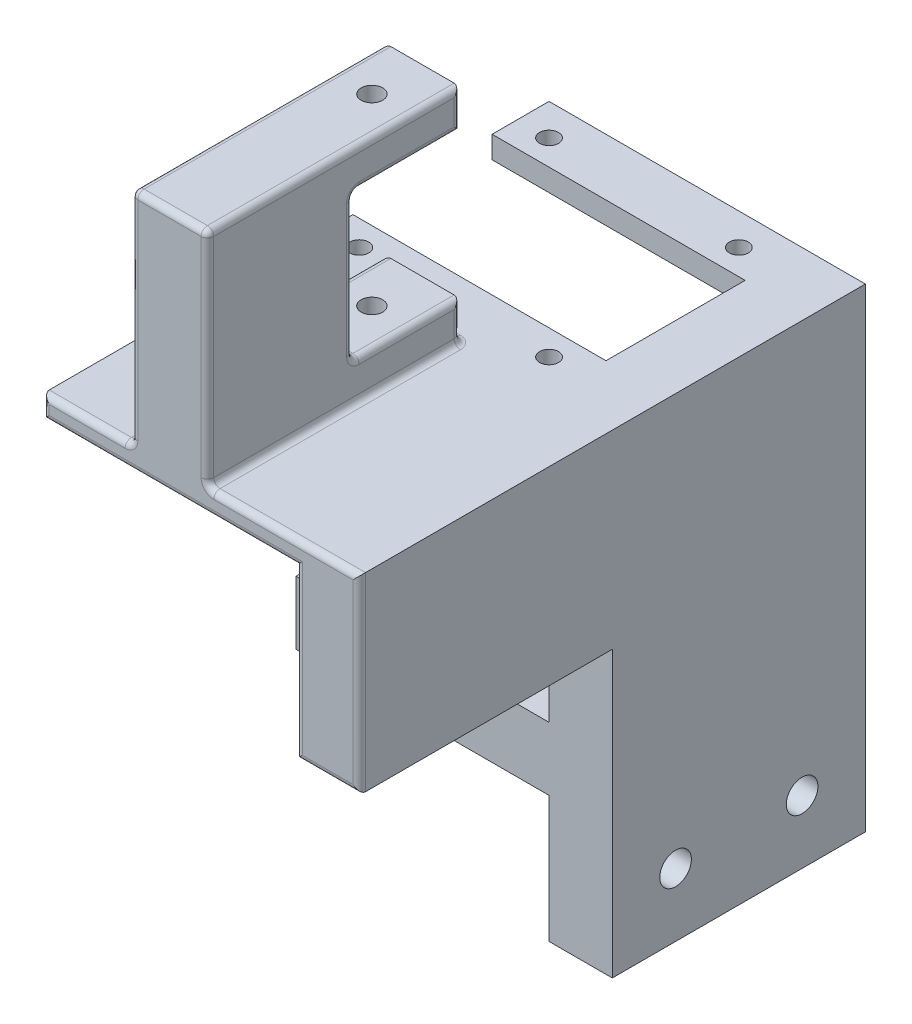
SolidWorks part; units mm, degrees
ref_plane "Front Plane" through (0, 0, 0) normal (0, 0, 1) x (1, 0, 0)
ref_plane "Top Plane" through (0, 0, 0) normal (0, 1, 0) x (1, 0, 0)
ref_plane "Right Plane" through (0, 0, 0) normal (1, 0, 0) x (0, 0, -1)
sketch "Sketch1" plane through (0, 0, 0) normal (1, 0, 0) x (0, 0, -1)
  line L0 (0, 27.5) -> (0, -27.5) construction
  line L5 (-20, 55) -> (20, 55)
  line L6 (-20, 55) -> (-20, 0)
  line L7 (-20, 0) -> (20, 0)
  line L8 (20, 55) -> (20, 0)
  line L9 (-20, 55) -> (20, 0) construction
  line L10 (-20, 0) -> (20, 55) construction
  line L11 (22, 0) -> (-22, 0) construction
  line L13 (-20, -20) -> (20, -20)
  line L14 (-20, -20) -> (-20, 0)
  line L15 (-20, 0) -> (20, 0)
  line L16 (20, -20) -> (20, 0)
  line L17 (-20, -20) -> (20, 0) construction
  line L18 (-20, 0) -> (20, -20) construction
  line L19 (10, -15) -> (-10, -15) construction
  line L20 (10, -15) -> (10, -5) construction
  line L21 (10, -5) -> (-10, -5) construction
  line L22 (-10, -15) -> (-10, -5) construction
  line L23 (10, -15) -> (-10, -5) construction
  line L24 (10, -5) -> (-10, -15) construction
  circle A0 centre (-10, -10) radius 2.5
  circle A1 centre (10, -10) radius 2.5
  point P1 (0, 27.5)
  point P10 (0, -10)
  point P11 (0, -10)
  dimension "D5" = 5
  dimension "D1" = 55
  dimension "D2" = 40
  dimension "D3" = 20
  dimension "D4" = 20
extrude "Boss-Extrude1" add sketch "Sketch1" along normal blind 10 contours L8 L5 L6 L7 | L13 L16 L7 L14 A1 A0 region at (0, 27.5, 0) region at (0, -10, 0)
sketch "Sketch3" plane through (0, 0, 0) normal (-1, 0, 0) x (0, 0, 1)
  line L0 (20, 55) -> (20, -20) construction
  line L1 (-20, 10) -> (20, 10)
  line L2 (-20, 10) -> (-20, 0)
  line L3 (-20, 0) -> (20, 0)
  line L4 (20, 10) -> (20, 0)
  line L5 (-20, 10) -> (20, 0) construction
  line L6 (-20, 0) -> (20, 10) construction
  dimension "D1" = 10
extrude "Boss-Extrude2" add sketch "Sketch3" along normal blind 40
sketch "Sketch4" plane through (0, 0, 0) normal (-1, 0, 0) x (0, 0, 1)
  line L13 (-20, 55) -> (-11, 55)
  line L14 (-20, 55) -> (-20, 51.5)
  line L15 (-20, 51.5) -> (-11, 51.5)
  line L16 (-11, 55) -> (-11, 51.5)
  dimension "D1" = 9
  dimension "D2" = 3.5
extrude "Boss-Extrude3" add sketch "Sketch4" along normal blind 40
sketch "Sketch5" plane through (0, 55, 0) normal (0, 1, 0) x (1, 0, 0)
  line L1 (-40, 20) -> (-35, 20) construction
  line L2 (-40, 20) -> (-40, 15) construction
  line L3 (-40, 15) -> (-35, 15) construction
  line L4 (-35, 20) -> (-35, 15) construction
  line L5 (10, 20) -> (-40, 20) construction
  line L7 (0, 20) -> (-5, 20) construction
  line L8 (0, 20) -> (0, 15) construction
  line L9 (0, 15) -> (-5, 15) construction
  line L10 (-5, 20) -> (-5, 15) construction
  circle A0 centre (-35, 15) radius 1.5
  circle A1 centre (-5, 15) radius 1.5
  dimension "D3" = 3
  dimension "D7" = 3
  dimension "D1" = 5
  dimension "D2" = 5
  dimension "D4" = 5
  dimension "D5" = 5
  dimension "D6" = 30
extrude "Cut-Extrude1" cut sketch "Sketch5" against normal up to next
mirror "Mirror2" about plane through (0, 0, 0) normal (0, 0, 1) of "Cut-Extrude1", "Boss-Extrude3"
sketch "Sketch7" plane through (0, 0, 20) normal (0, 0, 1) x (1, 0, 0)
  line L0 (0, -22) -> (0, 22) construction
  line L1 (-40, 55) -> (0, 55)
  line L2 (-40, 55) -> (-40, 51.5)
  line L3 (-40, 51.5) -> (0, 51.5)
  line L4 (0, 55) -> (0, 51.5)
  line L5 (-20, 51.5) -> (-20, 55) construction
  line L6 (-40, 53.25) -> (0, 53.25) construction
  line L7 (-40, 51.5) -> (0, 51.5) construction
  line L8 (10, 55) -> (10, -20) construction
  line L9 (0, 55) -> (10, 55)
  line L10 (0, 55) -> (0, 25)
  line L11 (0, 25) -> (10, 25)
  line L12 (10, 55) -> (10, 25)
  line L13 (5, 25) -> (5, 55) construction
  line L14 (0, 40) -> (10, 40) construction
  point P199 (5, 40)
  point P296 (-20, 53.25)
  line M2 (10, 55) -> (-40, 55)
  line M3 (-40, 55) -> (-40, 51.5)
  line M4 (-40, 51.5) -> (0, 51.5)
  line M5 (0, 51.5) -> (0, 10)
  line M11 (10, -20) -> (10, 55)
  dimension "D1" = 30
extrude "Boss-Extrude4" add sketch "Sketch7" along normal blind 40 contours L4 M2 M3 M4 | L11 L4 M5 M11 M2 region at (-20, 53.25, 20) region at (5, 40, 20)
sketch "Sketch8" plane through (0, 55, 0) normal (0, 1, 0) x (1, 0, 0)
  line L0 (10, -60) -> (-40, -60) construction
  line L1 (-26, -60) -> (-14, -60)
  line L2 (-26, -60) -> (-26, -20)
  line L3 (-26, -20) -> (-14, -20)
  line L4 (-14, -60) -> (-14, -20)
  line L5 (-20, -20) -> (-20, -60) construction
  line L6 (-26, -40) -> (-14, -40) construction
  line L7 (-40, -11) -> (-40, -60) construction
  line L8 (0, -41.25) -> (0, 41.25) construction
  point P100 (-20, -40)
  dimension "D1" = 12
  dimension "D2" = 40
extrude "Boss-Extrude5" add sketch "Sketch8" along normal blind 35
sketch "Sketch9" plane through (0, 0, 20) normal (0, 0, -1) x (-1, 0, 0)
  line L0 (14, 90) -> (14, 55) construction
  line L1 (14, 84) -> (26, 84)
  line L2 (14, 84) -> (14, 61)
  line L3 (14, 61) -> (26, 61)
  line L4 (26, 84) -> (26, 61)
  line L5 (20, 61) -> (20, 84) construction
  line L6 (14, 72.5) -> (26, 72.5) construction
  line L7 (26, 90) -> (26, 55) construction
  line L8 (14, 90) -> (26, 90) construction
  line L9 (-10, 55) -> (40, 55) construction
  point P172 (20, 72.5)
  dimension "D1" = 6
  dimension "D2" = 6
extrude "Cut-Extrude2" cut sketch "Sketch9" against normal blind 17
sketch "Sketch10" plane through (0, 90, 0) normal (0, 1, 0) x (1, 0, 0)
  line L0 (-20, -1038.2105) -> (-20, 48961.7895) construction
  line L1 (-26, -20) -> (-26, -60) construction
  line L2 (-14, -60) -> (-14, -20) construction
  line L4 (-14, -20) -> (-26, -20) construction
  circle A0 centre (-20, -28) radius 1.7
  dimension "D1" = 3.4
  dimension "D2" = 8
extrude "Cut-Extrude3" cut sketch "Sketch10" against normal up to surface (38.5 mm away) and the other way through all contours A0 up to face at (-35, 51.5, 13.5)
fillet "Fillet1" radius 1 27 edges at (-20, 55, 20) (-40, 53.25, 60) (-33, 55, 60) (-20, 90, 60) (-2, 55, 60) (10, 40, 60) (5, 25, 60) (0, 38.25, 60) (-20, 51.5, 60) (-14, 61, 28.5) (-14, 58, 20) (-14, 55, 40) (-14, 72.5, 60) (-14, 90, 40) (-14, 87, 20) (-14, 84, 28.5) (-26, 90, 40) (-26, 72.5, 60) (-26, 55, 40) (-26, 58, 20) (-26, 61, 28.5) (-26, 84, 28.5) (-26, 87, 20) (-20, 84, 37) (-26, 72.5, 37) (-20, 61, 37) (-14, 72.5, 37)
